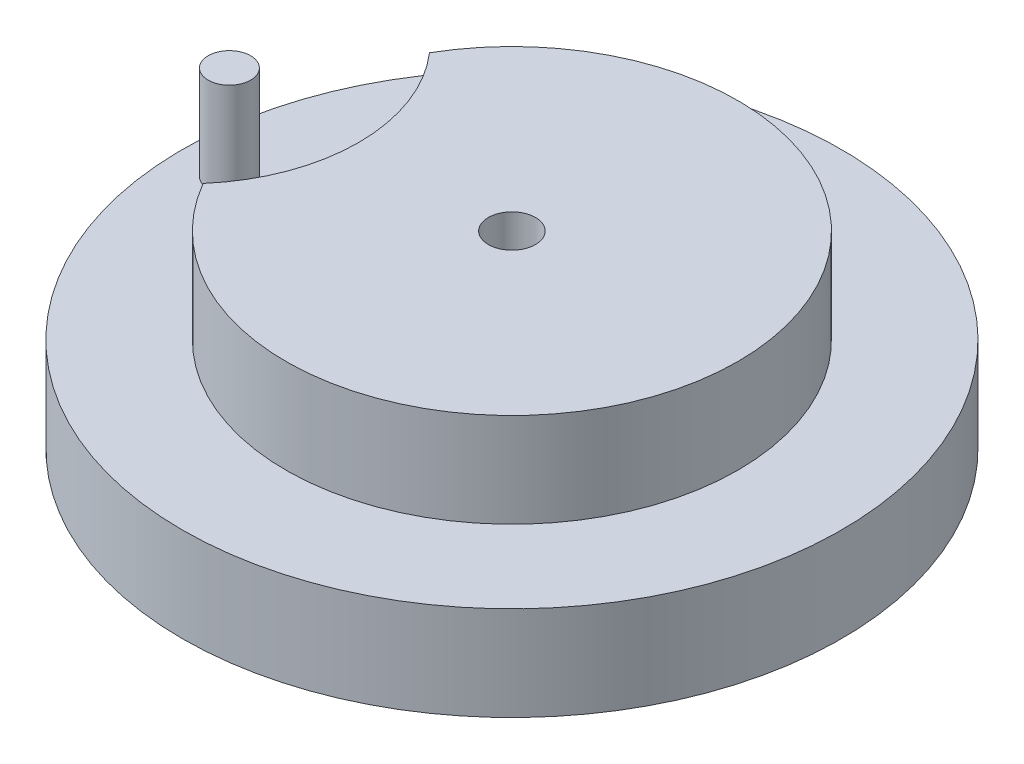
SolidWorks part; units mm, degrees
ref_plane "前基準面" through (0, 0, 0) normal (0, 0, 1) x (1, 0, 0)
ref_plane "上基準面" through (0, 0, 0) normal (0, 1, 0) x (1, 0, 0)
ref_plane "右基準面" through (0, 0, 0) normal (1, 0, 0) x (0, 0, -1)
sketch "草圖2" plane through (0, 0, 0) normal (0, 1, 0) x (1, 0, 0)
  circle A0 centre (0, 0) radius 35
  circle A1 centre (0, 0) radius 2.5
  dimension "D1" = 70
  dimension "D2" = 5
extrude "填料-伸長1" add sketch "草圖2" along normal blind 10
sketch "草圖3" plane through (0, 10, 0) normal (0, 1, 0) x (1, 0, 0)
  line L0 (-25.0434, 0) -> (28.3779, 0) construction
  line L1 (0, 21.5881) -> (0, -21.7622) construction
  circle A2 centre (0, 0) radius 2.5 construction
  circle A3 centre (0, 0) radius 2.5
  arc A4 (-20.7733, -12.0195) -> (-20.7733, 12.0195) centre (0, 0) ccw
  arc A5 (-20.7733, -12.0195) -> (-20.7733, 12.0195) centre (-34.5925, 0) ccw
  circle A6 centre (-30, 0) radius 2.25
  point P5 (-29.5744, 5.0354)
  point P6 (-25.0434, 0)
  point P7 (0, 0)
  point P9 (30, 0)
  point P15 (0.5741, 0)
  point P18 (0, 0)
  point P19 (0, 0)
  dimension "D1" = 4.5
  dimension "D3" = 24
  dimension "D4" = 18.315
  dimension "D2" = 30
  dimension "D5" = 34.5925
extrude "填料-伸長2" add sketch "草圖3" along normal blind 10
